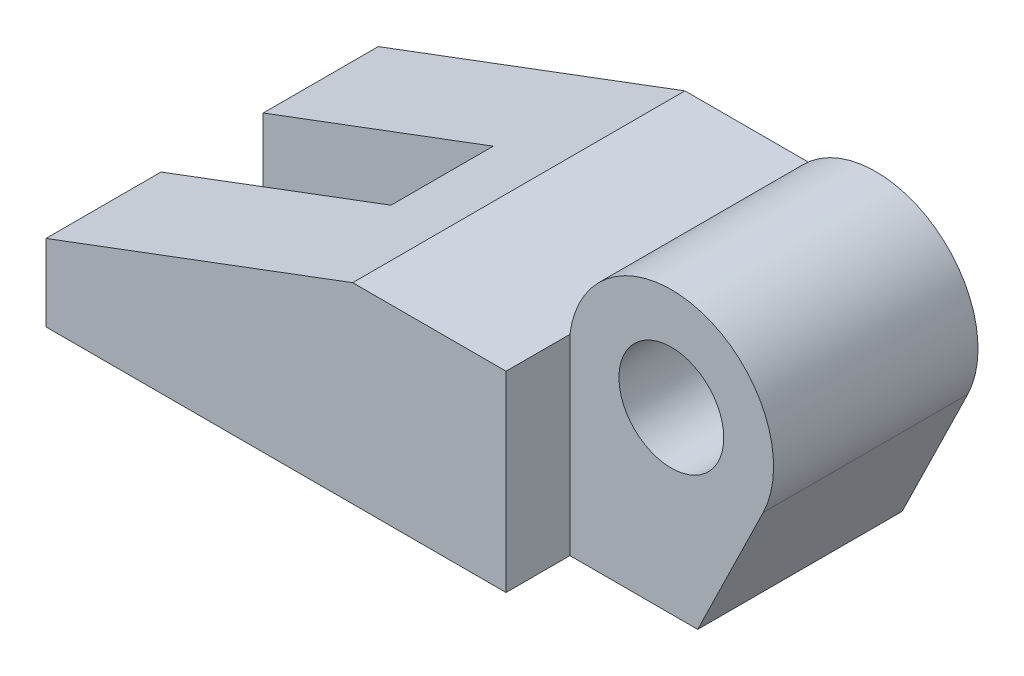
SolidWorks part; units mm, degrees
ref_plane "Front Plane" through (0, 0, 0) normal (0, 0, 1) x (1, 0, 0)
ref_plane "Top Plane" through (0, 0, 0) normal (0, 1, 0) x (1, 0, 0)
ref_plane "Right Plane" through (0, 0, 0) normal (1, 0, 0) x (0, 0, -1)
sketch "Sketch1" plane through (0, 0, 0) normal (0, 0, 1) x (1, 0, 0)
  line L0 (-18, -1.5) -> (6, 7.5)
  line L1 (6, 7.5) -> (18, 7.5)
  line L2 (-18, -1.5) -> (-18, -7.5)
  line L3 (-18, -7.5) -> (18, -7.5)
  line L4 (18, 7.5) -> (18, -7.5)
  line L5 (-18, 7.5) -> (18, -7.5) construction
  line L6 (-18, -7.5) -> (18, 7.5) construction
  line L7 (-18, 7.5) -> (6, 7.5) construction
  line L8 (-18, 7.5) -> (-18, -1.5) construction
  point P0 (0, 0)
  dimension "D1" = 36
  dimension "D2" = 15
  dimension "D3" = 6
  dimension "D4" = 12
extrude "Boss-Extrude2" add sketch "Sketch1" along normal blind 13 and the other way blind 13
sketch "Sketch3" plane through (0, -7.5, 0) normal (0, -1, 0) x (1, 0, 0)
  line L0 (-18, -13) -> (-18, 13) construction
  line L1 (-18, -4) -> (0, -4)
  line L2 (-18, -4) -> (-18, 4)
  line L3 (-18, 4) -> (0, 4)
  line L4 (0, -4) -> (0, 4)
  line L5 (-18, -13) -> (18, -13) construction
  dimension "D1" = 9
  dimension "D2" = 8
  dimension "D3" = 18
extrude "Cut-Extrude2" cut sketch "Sketch3" against normal through all
sketch "Sketch4" plane through (0, 0, 0) normal (0, 0, 1) x (1, 0, 0)
  line L0 (18, 7.5) -> (18, -7.5)
  line L1 (18, -7.5) -> (28, -7.5)
  line L2 (-22.0495, 6.5) -> (25.8842, 6.5) construction
  line L3 (28, -7.5) -> (33.125, 2.9876)
  arc A0 (33.125, 2.9876) -> (18, 7.5) centre (25.9373, 6.5) ccw
  dimension "D4" = 8
  dimension "D1" = 10
  dimension "D2" = 15
  dimension "D3" = 14
extrude "Boss-Extrude3" add sketch "Sketch4" along normal blind 8 and the other way blind 8
sketch "Sketch5" plane through (0, 0, 8) normal (0, 0, 1) x (1, 0, 0)
  circle A0 centre (25.9373, 6.5) radius 4.1
  arc A1 (33.125, 2.9876) -> (18, 7.5) centre (25.9373, 6.5) ccw construction
extrude "Cut-Extrude3" cut sketch "Sketch5" against normal through all
